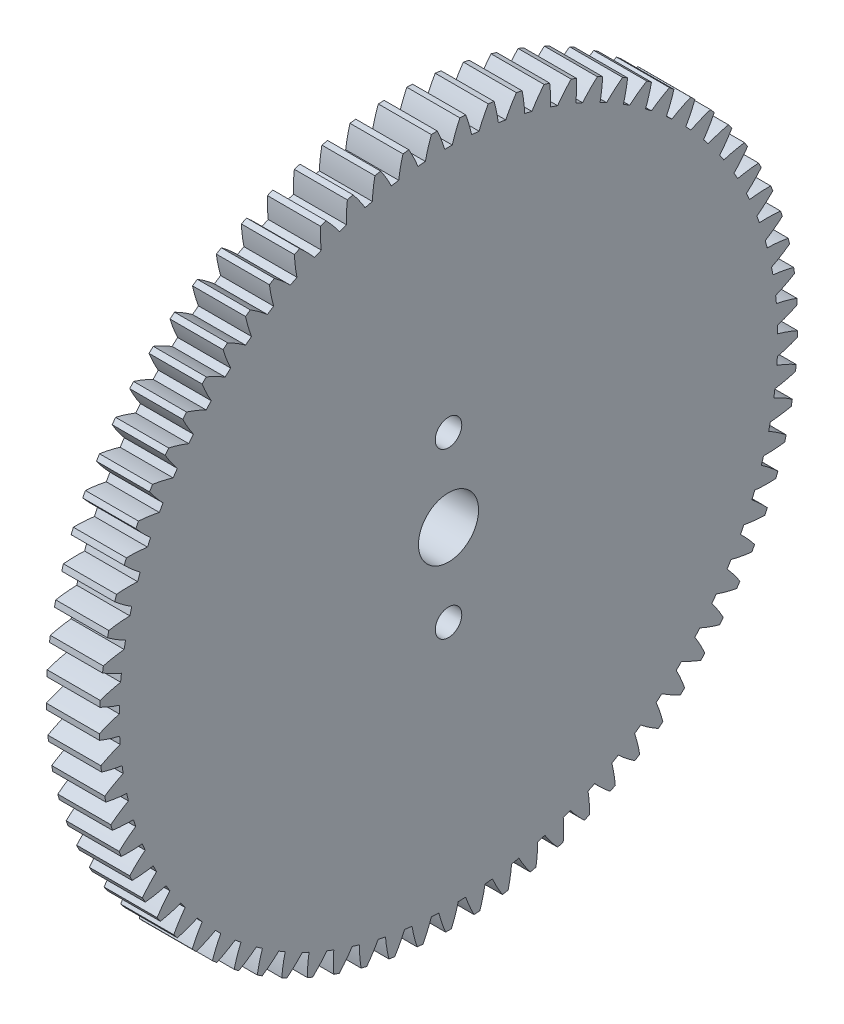
SolidWorks part; units mm, degrees
ref_plane "Plane1" through (0, 0, 0) normal (0, 0, 1) x (1, 0, 0)
ref_plane "Plane2" through (0, 0, 0) normal (0, 1, 0) x (1, 0, 0)
ref_plane "Plane3" through (0, 0, 0) normal (1, 0, 0) x (0, 0, -1)
sketch "HoldingSke" plane through (0, 0, 0) normal (0, 1, 0) x (1, 0, 0)
  line L0 (0, 0) -> (0.225, -0.9744)
  line L1 (-15, 0) -> (100, 0) construction
  line L2 (0, 0) -> (-2.1039, 2.3779)
  line L3 (0, 0) -> (-11.863, 4.5341)
  line L4 (0, 0) -> (1.9427, 8.4147)
  line L5 (0, 0) -> (-46.8476, -17.4728)
  line L6 (0, 0) -> (-1.6579, -1.1186)
  line L7 (-2.1039, 2.3779) -> (8.6586, 51.2059)
  line L8 (-76.2, 54.61) -> (-76.1, 54.61)
  line L9 (-71.009, 38.7566) -> (-53.1078, 45.2721)
  line L10 (-76.2, 71.12) -> (104.1128, 71.12)
  line L11 (0, 0) -> (-2, 0)
  line L12 (-76.2, 101.6) -> (-76.162, 101.6)
  line L13 (24.9733, 27.94) -> (52.9518, 28.4284)
  line L14 (24.9733, 27.94) -> (24.9743, 27.94)
  line L15 (24.9733, 27.94) -> (100.4006, 29.5858)
  line L16 (-63.627, -1) -> (-12.827, -1)
  circle A0 centre (0, 0) radius 0.5
  circle A1 centre (0, 0) radius 37.249
  circle A2 centre (0, 0) radius 37.5
  circle A3 centre (0, 0) radius 0.5
  dimension "MHD" = 74.498
  dimension "Hub_dia" = 75
  dimension "Bore" = 1
  dimension "MBD" = 1
  dimension "Num_teeth" = 77
  dimension "Pitch" = 1
  dimension "Overall_len" = 50
  dimension "Show_teeth" = 77
  dimension "Thickness" = 2
  dimension "OAL" = 50.0001
  dimension "T_dim" = 0.1
  dimension "Ap" = 20
  dimension "H" = 19.05
  dimension "Pitch_radius" = 180.3128
  dimension "Width" = 2
  dimension "Backlash" = 0.038
  dimension "Addendum_fac" = 1
  dimension "Dedendum_fac" = 1.25
  dimension "Clearance_fac" = 0.25
  dimension "Dedendum_add" = 0.001
  dimension "Module" = 1
sketch "BasProSke" plane through (0, 0, 0) normal (0, 1, 0) x (1, 0, 0)
  line L0 (-10, 0) -> (60, 0) construction
  line L1 (0, 0) -> (0, 39.5)
  line L2 (0, 0) -> (2, 0)
  line L3 (2, 0) -> (2, 39.5)
  line L4 (2, 39.5) -> (0, 39.5)
  dimension "Thickness" = 2
  dimension "Diameter" = 79
revolve "Base-Revolve" add sketch "BasProSke" angle 360 about L0
sketch "TooCutSke" plane through (0, 0, 0) normal (1, 0, 0) x (0, 0, -1)
  line L1 (0, 0) -> (0, 107) construction
  line L2 (0, 0) -> (-0.8518, 38.4906) construction
  line L3 (0, 0) -> (-3.1402, 76.9225) construction
  line L4 (-0.8518, 38.4906) -> (-1.5701, 38.4613) construction
  arc A0 (0.4217, 37.2466) -> (-0.4217, 37.2466) centre (0, 0) ccw
  arc A1 (1.2943, 39.5042) -> (-1.2943, 39.5042) centre (0, 0) ccw
  circle A2 centre (0, 0) radius 38.5 construction
  circle A3 centre (0, 0) radius 36.1782 construction
  arc A4 (-0.4217, 37.2466) -> (-1.2943, 39.5042) centre (-15.1779, 32.8404) ccw
  arc A5 (1.2943, 39.5042) -> (0.4217, 37.2466) centre (15.1779, 32.8404) ccw
  dimension "Root_dia" = 74.498
  dimension "Overcut_dia" = 79.0508
  dimension "Pitch_dia" = 77
  dimension "Base_dia" = 72.3563
  dimension "Flank_rad" = 15.4
  dimension "Half_ang" = 2.338
  dimension "Half_CT" = 0.7188
extrude "ToothCut" cut sketch "TooCutSke" along normal through all
fillet "Breaks" [suppressed] radius 0.02 tangent propagation no
fillet "RootFillets" [suppressed] radius 0.251
pattern_circular "TeethCuts" count 77 every 4.675 about axis through (-10, 0, 0) along (1, 0, 0) of "ToothCut", "RootFillets", "Breaks"
sketch "HubNeaOneSke" plane through (0, 0, 0) normal (-1, 0, 0) x (0, 0, 1)
  circle A0 centre (0, 0) radius 37.249
  dimension "Diameter" = 74.498
extrude "HubNearOne" [suppressed] add sketch "HubNeaOneSke" along normal blind 48.0001
sketch "HubNeaBotSke" plane through (0, 0, 0) normal (-1, 0, 0) x (0, 0, 1)
  circle A0 centre (0, 0) radius 37.249
  dimension "Diameter" = 74.498
extrude "HubNearBoth" [suppressed] add sketch "HubNeaBotSke" along normal blind 24
ref_plane "FarPln" through (2, 0, 0) normal (1, 0, 0) x (0, 0, -1)
sketch "HubFarSke" plane through (2, 0, 0) normal (1, 0, 0) x (0, 0, -1)
  circle A0 centre (0, 0) radius 37.249
  dimension "Diameter" = 74.498
extrude "HubFar" [suppressed] add sketch "HubFarSke" along normal blind 24
sketch "BorSke" plane through (0, 0, 0) normal (1, 0, 0) x (0, 0, -1)
  circle A0 centre (0, 0) radius 3.4
  circle A1 centre (0, -9.3) radius 1.5
  circle A2 centre (0, 9.3) radius 1.5
  dimension "Diameter" = 6.8
  dimension "D3" = 3
  dimension "D4" = 3
  dimension "D1" = 9.3
  dimension "D2" = 9.3
extrude "Bore" cut sketch "BorSke" along normal mid plane 100.0001
sketch "KeySke" plane through (0, 0, 0) normal (1, 0, 0) x (0, 0, -1)
  line L0 (-0.05, 0) -> (-0.05, 0.6)
  line L1 (-0.05, 0.6) -> (0.05, 0.6)
  line L2 (0.05, 0.6) -> (0.05, 0)
  line L3 (0, 0) -> (0, 34) construction
  line L4 (-0.05, 0) -> (0.05, 0)
  dimension "Offset" = 0.6
  dimension "Width" = 0.1
extrude "Keyway" [suppressed] cut sketch "KeySke" along normal mid plane 100.0001
pattern_circular "Keyway2" [suppressed] count 2 every 90 about axis through (-10, 0, 0) along (1, 0, 0) reverse direction yes
scale "Scale1" scale about centroid uniform scaling no x scale factor 3 y scale factor 1 z scale factor 1
equation "' \"Module@HoldingSke\" = 6.35"
equation "' \"Num_teeth@HoldingSke\" = 12"
equation "' \"Ap@HoldingSke\" =  20"
equation "' \"Ap@HoldingSke\" = 20"
equation "' \"Width@HoldingSke\" = 0.5 * 25.4"
equation "' \"Hub_dia@HoldingSke\"= 1 * 25.4"
equation "' \"Hub_dia@HoldingSke\" = 1 * 25.4"
equation "' \"Overall_len@HoldingSke\" = 1.0 * 25.4"
equation "' \"Bore@HoldingSke\" = 0.75 * 25.4"
equation "' \"T_dim@HoldingSke\" = 0.1 * 25.4"
equation "' \"Width@KeySke\" = 0.25 * 25.4"
equation "' \"Show_teeth@HoldingSke\" = 13"
equation "' \"Backlash@HoldingSke\" = 0.009 * 25.4"
equation "' \"Addendum_fac@HoldingSke\" = 1.0"
equation "' \"Dedendum_fac@HoldingSke\" = 1.25"
equation "' \"Dedendum_add@HoldingSke\" = 0.00005 * 25.4"
equation "' \"Clearance_fac@HoldingSke\" = 0.25"
equation "\"Pitch@HoldingSke\" = 1 / \"Module@HoldingSke\""
equation "\"Overcut_dia@TooCutSke\" = (\"Num_teeth@HoldingSke\" + 2 * \"Addendum_fac@HoldingSke\") / \"Pitch@HoldingSke\" + 0.002 * 25.4"
equation "\"Pitch_dia@TooCutSke\" = \"Num_teeth@HoldingSke\" / \"Pitch@HoldingSke\""
equation "\"Base_dia@TooCutSke\" = \"Num_teeth@HoldingSke\" / \"Pitch@HoldingSke\" * cos((\"Ap@HoldingSke\"  * 3.14159265 / 180))"
equation "\"Root_dia@TooCutSke\" = (\"Num_teeth@HoldingSke\" + 2) / \"Pitch@HoldingSke\" - 2 * (\"Addendum_fac@HoldingSke\" + \"Dedendum_fac@HoldingSke\") / \"Pitch@HoldingSke\" - \"Dedendum_add@HoldingSke\" * 2"
equation "\"Half_ang@TooCutSke\" = 180 / \"Num_teeth@HoldingSke\""
equation "\"Half_CT@TooCutSke\" = \"Num_teeth@HoldingSke\" / \"Pitch@HoldingSke\" * sin((3.14159265 / 2 / \"Num_teeth@HoldingSke\")) / 2 - 7 * \"Backlash@HoldingSke\" / 4"
equation "\"Flank_rad@TooCutSke\" = \"Num_teeth@HoldingSke\" / \"Pitch@HoldingSke\" / 5"
equation "\"Radius@RootFillets\" = \"Clearance_fac@HoldingSke\" / \"Pitch@HoldingSke\" + \"Dedendum_add@HoldingSke\""
equation "\"Break_rad@Breaks\" = 0.02 / \"Pitch@HoldingSke\""
equation "\"Thickness@HoldingSke\" = \"Width@HoldingSke\""
equation "\"OAL@HoldingSke\" = \"Thickness@HoldingSke\""
equation "\"MHD@HoldingSke\" = (\"Num_teeth@HoldingSke\" + 2) / \"Pitch@HoldingSke\" - 2 * (\"Addendum_fac@HoldingSke\" + \"Dedendum_fac@HoldingSke\")  / \"Pitch@HoldingSke\" - \"Dedendum_add@HoldingSke\" * 2"
equation "\"MBD@HoldingSke\" = (\"Num_teeth@HoldingSke\" + 2) / \"Pitch@HoldingSke\" - 2 * (\"Addendum_fac@HoldingSke\" + \"Dedendum_fac@HoldingSke\")  / \"Pitch@HoldingSke\" - \"Dedendum_add@HoldingSke\" * 2 - 0.002 * 25.4"
equation "\"MHD@HoldingSke\" = ((sgn( \"MHD@HoldingSke\" - \"Hub_dia@HoldingSke\" )-1)*( \"MHD@HoldingSke\" - \"Hub_dia@HoldingSke\" ))/-2+ \"Hub_dia@HoldingSke\""
equation "\"MBD@HoldingSke\" = ((sgn( \"MBD@HoldingSke\" - \"Bore@HoldingSke\" )-1)*( \"MBD@HoldingSke\" - \"Bore@HoldingSke\" ))/-2+ \"Bore@HoldingSke\""
equation "\"OAL@HoldingSke\" = ((sgn( \"OAL@HoldingSke\" - \"Overall_len@HoldingSke\" )+1)*( \"OAL@HoldingSke\" - \"Overall_len@HoldingSke\" ))/2 + \"Overall_len@HoldingSke\" + 0.000002 * 25.4"
equation "\"Num_teeth@TeethCuts\" = int( \"Show_teeth@HoldingSke\" ) + 1"
equation "\"Num_teeth@TeethCuts\" = ((sgn( \"Num_teeth@TeethCuts\" - \"Num_teeth@HoldingSke\" )-1)*( \"Num_teeth@TeethCuts\" - \"Num_teeth@HoldingSke\" ))/-2+ \"Num_teeth@HoldingSke\""
equation "\"Num_teeth@TeethCuts\" = ((sgn( \"Num_teeth@TeethCuts\" - 2.0)+1)*( \"Num_teeth@TeethCuts\" - 2.0))/2 +2.0"
equation "\"Angle@TeethCuts\" = 360.0 / \"Num_teeth@HoldingSke\""
equation "\"Diameter@BasProSke\" = (\"Num_teeth@HoldingSke\" + 2 * \"Addendum_fac@HoldingSke\") / \"Pitch@HoldingSke\""
equation "\"Thickness@BasProSke\"  = \"Thickness@HoldingSke\""
equation "' \"Fillet_rad@BasProSke\" =  \"Thickness@HoldingSke\" * 0.05"
equation "' \"Fillet_rad@BasProSke\" = \"Thickness@HoldingSke\" * 0.05"
equation "\"MHD@HoldingSke\" = ((sgn( \"MHD@HoldingSke\" - \"Root_dia@TooCutSke\" )-1)*( \"MHD@HoldingSke\" - \"Root_dia@TooCutSke\" ))/-2+ \"Root_dia@TooCutSke\""
equation "\"Diameter@HubNeaOneSke\" = \"MHD@HoldingSke\""
equation "\"Length@HubNearOne\" = \"OAL@HoldingSke\" - \"Thickness@BasProSke\""
equation "\"Diameter@HubNeaBotSke\" = \"MHD@HoldingSke\""
equation "\"Length@HubNearBoth\" = ( \"OAL@HoldingSke\" - \"Thickness@BasProSke\" ) / 2.0"
equation "\"Thickness@FarPln\" = \"Thickness@BasProSke\""
equation "\"Diameter@HubFarSke\" = \"MHD@HoldingSke\""
equation "\"Length@HubFar\" = ( \"OAL@HoldingSke\" - \"Thickness@BasProSke\" ) / 2.0"
equation "\"Diameter@BorSke\"=6.8mm"
equation "\"D1@Bore\" = \"OAL@HoldingSke\" * 2.0"
equation "\"D1@Keyway\" = \"OAL@HoldingSke\" * 2.0"
equation "\"Offset@KeySke\" = \"T_dim@HoldingSke\" + \"MBD@HoldingSke\" / 2.0"
